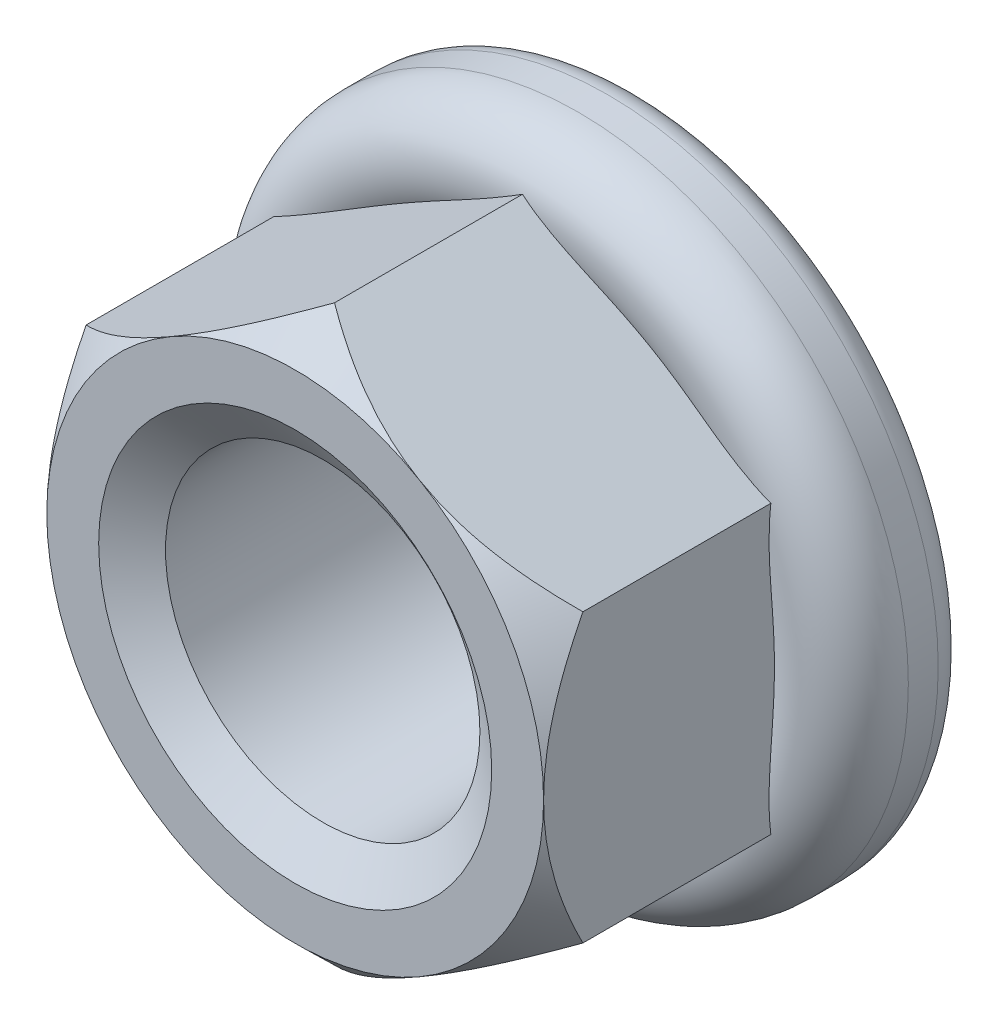
SolidWorks part; units mm, degrees
extrude "BaseNut" add sketch "BaseNutSke" against normal blind 5.5626
sketch "BaseNutSke" plane through (0, 0, 0) normal (0, 0, 1) x (1, 0, 0)
  line L6 (4.0132, 2.317) -> (4.0132, -2.317)
  line L7 (-4.0132, 2.317) -> (-4.0132, -2.317)
  line L8 (4.0132, 2.317) -> (0, 4.634)
  line L9 (0, 4.634) -> (-4.0132, 2.317)
  line L10 (-4.0132, -2.317) -> (0, -4.634)
  line L11 (0, -4.634) -> (4.0132, -2.317)
  circle A0 centre (0, 0) radius 2.54
  dimension "D2" = 4.0132
  dimension "D3" = 4.0132
  dimension "D1" = 120
  dimension "D4" = 4.0132
cosmetic thread "ThreadCosmetic" [suppressed] parameters "D1"=4.6479, "Thread_major"=6.35
ref_plane "Plane1" through (0, 0, 0) normal (0, 0, 1) x (1, 0, 0)
ref_plane "Plane2" through (0, 0, 0) normal (0, 1, 0) x (1, 0, 0)
ref_plane "Plane3" through (0, 0, 0) normal (1, 0, 0) x (0, 0, -1)
sketch "Sketch4" plane through (0, 0, 0) normal (1, 0, 0) x (0, 0, -1)
  line L0 (5.5626, 4.0132) -> (5.1562, 4.0132)
  line L1 (5.5626, 4.0132) -> (5.5626, 17.334)
  line L2 (5.1562, 17.334) -> (5.5626, 17.334)
  line L3 (5.1562, 17.334) -> (5.1562, 4.0132)
  line L4 (0, 0) -> (34.925, 0) construction
  line L6 (5.5626, 2.317) -> (5.5626, 4.634) construction
  line L7 (0, 4.0132) -> (-12.7, 4.0132)
  line L8 (0, 2.317) -> (0, 4.634) construction
  line L9 (0.635, 4.634) -> (0.635, 17.334)
  line L10 (0.635, 17.334) -> (-12.7, 17.334)
  line L11 (-12.7, 17.334) -> (-12.7, 4.0132)
  line L12 (0, 4.0132) -> (0.635, 4.634)
  line L14 (0, 2.317) -> (0, -2.317) construction
  line L15 (5.5626, 4.634) -> (0, 4.634) construction
  dimension "D1" = 4.0132
  dimension "D2" = 0.635
  dimension "D3" = 12.7
  dimension "D4" = 12.7
revolve "Bearing-Face" [suppressed] cut sketch "Sketch4" angle 360 about L4
sketch "Sketch3" plane through (0, 0, 0) normal (1, 0, 0) x (0, 0, -1)
  line L0 (5.5626, 4.0132) -> (4.9276, 4.634) construction
  line L1 (4.9276, 4.634) -> (4.9276, 17.334) construction
  line L2 (4.9276, 17.334) -> (18.2626, 17.334) construction
  line L3 (18.2626, 17.334) -> (18.2626, 4.0132) construction
  line L4 (18.2626, 4.0132) -> (5.5626, 4.0132) construction
  line L5 (5.5626, 2.317) -> (5.5626, 4.634) construction
  line L6 (5.5626, 4.634) -> (0, 4.634) construction
  line L7 (0, 0) -> (38.6776, 0) construction
  line L8 (5.5626, 0) -> (0, 0) construction
  line L9 (2.7813, 4.634) -> (2.7813, 44.222) construction
  line L10 (0.635, 17.334) -> (-12.7, 17.334)
  line L11 (-12.7, 17.334) -> (-12.7, 4.0132)
  line L12 (-12.7, 4.0132) -> (0, 4.0132)
  line L13 (0, 4.0132) -> (0.635, 4.634)
  line L14 (0.635, 4.634) -> (0.635, 17.334)
  line L16 (5.5626, 4.634) -> (0, 4.634) construction
  dimension "D1" = 4.0132
  dimension "D2" = 0.635
  dimension "D4" = 12.7
  dimension "D3" = 12.7
revolve "Double-Chamfer" cut sketch "Sketch3" angle 360 about L7
sketch "EndChamferSke" plane through (0, 0, 0) normal (1, 0, 0) x (0, 0, -1)
  line L0 (5.5372, 3.175) -> (5.0481, 2.4765)
  line L1 (5.588, 3.175) -> (5.5372, 3.175)
  line L2 (5.588, 3.175) -> (5.588, 2.4765)
  line L3 (5.588, 2.4765) -> (5.0481, 2.4765)
  line L6 (-0.0508, 3.175) -> (0, 3.175)
  line L7 (0, 3.175) -> (0.4891, 2.4765)
  line L9 (0.4891, 2.4765) -> (-0.0508, 2.4765)
  line L10 (-0.0508, 2.4765) -> (-0.0508, 3.175)
  line L11 (25.0375, 0) -> (38.388, 0) construction
  dimension "D1" = 35
  dimension "D2" = 0.0508
  dimension "ThreadMajor" = 3.175
  dimension "Offset1" = 5.588
sketch "ThdSchSke" plane through (0, 0, 0) normal (0, 1, 0) x (1, 0, 0)
  line L0 (-3.175, 0.0254) -> (-2.54, 0.47)
  line L1 (-2.54, 0.47) -> (-1.27, 0.47)
  line L2 (-1.27, 0.47) -> (-1.27, -0.4192)
  line L3 (-1.27, -0.4192) -> (-2.54, -0.4192)
  line L4 (-2.54, -0.4192) -> (-3.175, 0.0254)
  line L6 (0, 0.4788) -> (0, -2.9874) construction
  line L7 (3.175, 0.4788) -> (15.875, 0.4788) construction
  dimension "SideAngle" = 55
  dimension "D1" = 0.0254
  dimension "Thread_major" = 6.35
  dimension "OverCut" = 2.54
  dimension "Advance" = 0.9068
revolve "EndChamfer" cut sketch "EndChamferSke" angle 360 about L11
revolve "ThreadSchematic" [suppressed] cut sketch "ThdSchSke" angle 360 about L6
pattern_linear "ThdSchPat" [suppressed]
sketch "Sketch5" plane through (0, 0, 0) normal (1, 0, 0) x (0, 0, -1)
  line L0 (5.5626, 3.4755) -> (5.5626, 4.826)
  line L1 (5.0546, 5.334) -> (4.572, 5.334)
  line L2 (4.572, 3.4755) -> (5.5626, 3.4755)
  line L3 (-4.4998, 0) -> (10.8386, 0) construction
  line L4 (5.5626, 4.634) -> (5.5626, 2.317) construction
  line L8 (5.5626, 2.317) -> (5.5626, 4.634) construction
  arc A0 (4.572, 5.334) -> (4.572, 3.4755) centre (4.572, 4.4048) ccw
  arc A1 (5.5626, 4.826) -> (5.0546, 5.334) centre (5.0546, 4.826) ccw
  dimension "A_dia" = 10.668
  dimension "B_dia" = 9.652
  dimension "J" = 0.4826
revolve "Revolve1" add sketch "Sketch5" angle 360 about L3
equation "\"D2@BaseNutSke\" = \"Width_flats@BaseNutSke\" / 2"
equation "\"D3@BaseNutSke\" = \"Width_flats@BaseNutSke\" / 2"
equation "\"D1@Sketch3\" = \"Width_flats@BaseNutSke\" /2"
equation "\"D2@Sketch3\" = \"Thread_major@ThreadCosmetic\" *.1"
equation "\"D1@Sketch4\" = \"D2@BaseNutSke\""
equation "\"D2@Sketch4\" = \"Thread_major@ThreadCosmetic\" *.10"
equation "\"D4@BaseNutSke\" = \"D3@BaseNutSke\""
equation "\"Thread_major@ThdSchSke\" = \"Thread_major@ThreadCosmetic\""
equation "\"Tap_drill@ThdSchSke\" = \"Thread_min@BaseNutSke\""
equation "\"OverCut@ThdSchSke\" = \"Tap_drill@ThdSchSke\" * 0.5"
equation "\"Num_threads@ThdSchPat\" = int(  ( \"Thickness@BaseNut\" - 0.002 ) / \"Advance@ThdSchSke\" + 0.999 )  + 1"
equation "\"Advance@ThdSchPat\" = ( \"Thickness@BaseNut\" - 0.002 ) /  (\"Num_threads@ThdSchPat\" - 1) 'relax it"
equation "' \"Num_threads@ThdSchPat\" = \"Num_threads@ThdSchPat\" - sgn( \"Num_threads@ThdSchPat\" - 1) '---chamfered tips only---"
equation "\"ThreadMajor@EndChamferSke\" = \"Thread_major@ThreadCosmetic\" * 0.5"
equation "\"ChamferDepth@EndChamferSke\" = (\"Thread_major@ThreadCosmetic\" - \"Thread_min@BaseNutSke\") * 0.55"
equation "\"Offset1@EndChamferSke\" = \"Thickness@BaseNut\" + 0.001"
equation "\"Offset2@EndChamferSke\" = \"Offset1@EndChamferSke\" + 0.002"
